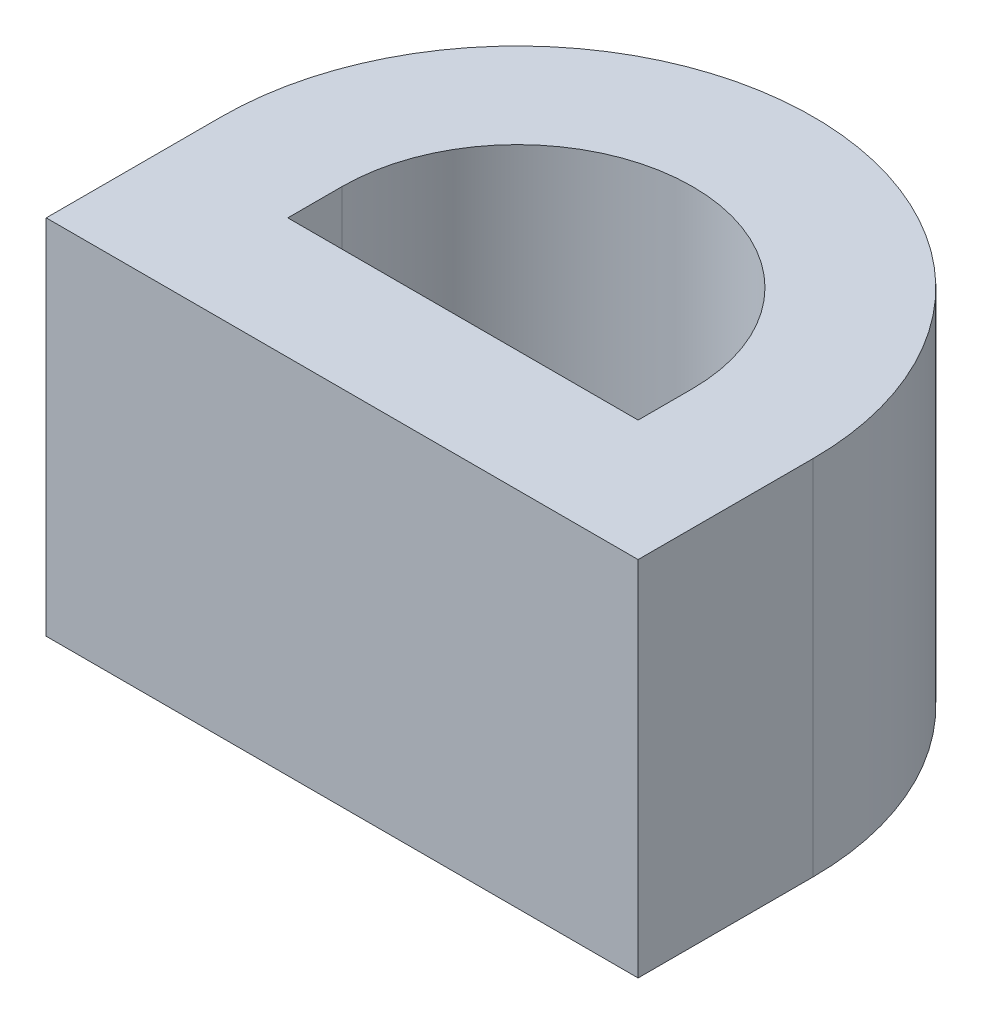
SolidWorks part; units mm, degrees
ref_plane "Front Plane" through (0, 0, 0) normal (0, 0, 1) x (1, 0, 0)
ref_plane "Top Plane" through (0, 0, 0) normal (0, 1, 0) x (1, 0, 0)
ref_plane "Right Plane" through (0, 0, 0) normal (1, 0, 0) x (0, 0, -1)
sketch "Sketch1" plane through (0, 0, 0) normal (0, 1, 0) x (1, 0, 0)
  line L0 (-4.9, -0.9) -> (-2.9, -0.9) construction
  line L1 (-2.9, 0) -> (2.9, 0)
  line L2 (-2.9, 0) -> (-2.9, -0.9)
  line L3 (-2.9, -0.9) -> (2.9, -0.9)
  line L4 (2.9, 0) -> (2.9, -0.9)
  line L5 (-4.9, 0) -> (4.9, 0)
  line L6 (-4.9, 0) -> (-4.9, -2.9)
  line L7 (-4.9, -2.9) -> (4.9, -2.9)
  line L8 (4.9, 0) -> (4.9, -2.9)
  line L9 (-2.9, -0.9) -> (-2.9, -2.9) construction
  circle A0 centre (0, 0) radius 2.9
  circle A1 centre (0, 0) radius 4.9
  dimension "D1" = 5.8
  dimension "D2" = 2
  dimension "D3" = 0.9
extrude "Boss-Extrude1" add sketch "Sketch1" along normal blind 4 contours L5 A1 A0 | L7 A1 L5 L4 L3 A0 | A1 L7 L8 | L5 A1 L7 A0 L3 L2 | A1 L6 L7 | A0 L3 region at (-3.3668, 0, 1.5742) region at (-3.9, 0, -0.1096) region at (3.3668, 0, 1.5742) region at (-4.6204, 0, 2.1898) region at (0, 0, 1.7297) region at (4.6204, 0, 2.1898)
extrude "Boss-Extrude2" add sketch "Sketch1<3>" against normal blind 2 contours L5 A1 A0 | A0 L2 L3 | A0 L3 L4 | L1 A0 | L3 A0 L1 | L5 A1 L7 A0 L3 L2 | L7 A1 L5 L4 L3 A0 | A1 L7 L8 | A1 L6 L7 | A0 L3 region at (0, 0, -1.2308) region at (-2.8572, 0, 0.6761) region at (-3.3668, 0, 1.5742) region at (-3.9, 0, -0.1096) region at (0, 0, 0.4463) region at (3.3668, 0, 1.5742) region at (2.8572, 0, 0.6761) region at (-4.6204, 0, 2.1898) region at (0, 0, 1.7297) region at (4.6204, 0, 2.1898)
sketch "Sketch1<3>" plane through (0, 0, 0) normal (0, 1, 0) x (1, 0, 0) same geometry as "Sketch1"
